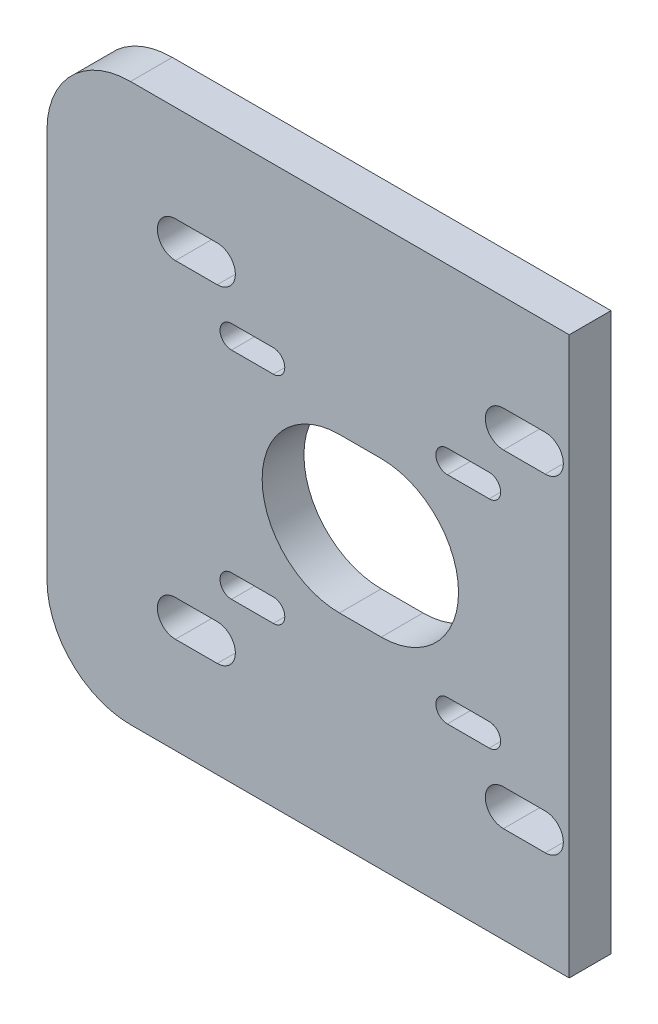
SolidWorks part; units mm, degrees
ref_plane "Alzado" through (0, 0, 0) normal (0, 0, 1) x (1, 0, 0)
ref_plane "Planta" through (0, 0, 0) normal (0, 1, 0) x (1, 0, 0)
ref_plane "Vista lateral" through (0, 0, 0) normal (1, 0, 0) x (0, 0, -1)
sketch "Croquis1" plane through (0, 0, 0) normal (0, 0, 1) x (1, 0, 0)
  line L1 (0, 0) -> (75, 0)
  line L2 (0, 0) -> (0, 80)
  line L3 (0, 80) -> (75, 80)
  line L4 (75, 0) -> (75, 80)
  dimension "D1" = 80
  dimension "D2" = 75
extrude "Saliente-Extruir1" add sketch "Croquis1" along normal blind 6
sketch "Croquis2" plane through (0, 0, 0) normal (0, 0, -1) x (-1, 0, 0)
  line L0 (0, 80) -> (0, 0) construction
  line L1 (0, 40) -> (-75, 40) construction
  line L4 (-75, 0) -> (-75, 80) construction
  line L7 (-42, 40) -> (-48, 40) construction
  line L10 (-42, 28.9) -> (-48, 28.9)
  line L19 (-42, 51.1) -> (-48, 51.1)
  line L20 (-26.5, 24.5) -> (-32.5, 24.5) construction
  line L21 (-26.5, 22.85) -> (-32.5, 22.85)
  line L22 (-26.5, 26.15) -> (-32.5, 26.15)
  line L23 (-57.5, 55.5) -> (-63.5, 55.5) construction
  line L24 (-57.5, 53.85) -> (-63.5, 53.85)
  line L25 (-57.5, 57.15) -> (-63.5, 57.15)
  line L26 (-57.5, 24.5) -> (-63.5, 24.5) construction
  line L27 (-57.5, 22.85) -> (-63.5, 22.85)
  line L28 (-57.5, 26.15) -> (-63.5, 26.15)
  line L29 (-26.5, 55.5) -> (-32.5, 55.5) construction
  line L30 (-26.5, 53.85) -> (-32.5, 53.85)
  line L31 (-26.5, 57.15) -> (-32.5, 57.15)
  line L32 (-18.45, 16.45) -> (-24.45, 16.45) construction
  line L33 (-18.45, 13.85) -> (-24.45, 13.85)
  line L34 (-18.45, 19.05) -> (-24.45, 19.05)
  line L35 (-65.55, 16.45) -> (-71.55, 16.45) construction
  line L36 (-21.45, 63.55) -> (-68.55, 63.55) construction
  line L37 (-21.45, 63.55) -> (-21.45, 16.45) construction
  line L38 (-21.45, 16.45) -> (-68.55, 16.45) construction
  line L39 (-68.55, 63.55) -> (-68.55, 16.45) construction
  line L40 (-21.45, 63.55) -> (-68.55, 16.45) construction
  line L41 (-21.45, 16.45) -> (-68.55, 63.55) construction
  line L42 (-65.55, 13.85) -> (-71.55, 13.85)
  line L43 (-65.55, 19.05) -> (-71.55, 19.05)
  line L44 (-18.45, 63.55) -> (-24.45, 63.55) construction
  line L45 (-18.45, 60.95) -> (-24.45, 60.95)
  line L46 (-18.45, 66.15) -> (-24.45, 66.15)
  line L47 (-65.55, 63.55) -> (-71.55, 63.55) construction
  line L48 (-65.55, 60.95) -> (-71.55, 60.95)
  line L49 (-65.55, 66.15) -> (-71.55, 66.15)
  arc A19 (-42, 28.9) -> (-42, 51.1) centre (-42, 40) ccw
  arc A20 (-48, 51.1) -> (-48, 28.9) centre (-48, 40) ccw
  arc A21 (-26.5, 22.85) -> (-26.5, 26.15) centre (-26.5, 24.5) ccw
  arc A22 (-32.5, 26.15) -> (-32.5, 22.85) centre (-32.5, 24.5) ccw
  arc A23 (-57.5, 53.85) -> (-57.5, 57.15) centre (-57.5, 55.5) ccw
  arc A24 (-63.5, 57.15) -> (-63.5, 53.85) centre (-63.5, 55.5) ccw
  arc A25 (-57.5, 22.85) -> (-57.5, 26.15) centre (-57.5, 24.5) ccw
  arc A26 (-63.5, 26.15) -> (-63.5, 22.85) centre (-63.5, 24.5) ccw
  arc A27 (-26.5, 53.85) -> (-26.5, 57.15) centre (-26.5, 55.5) ccw
  arc A28 (-32.5, 57.15) -> (-32.5, 53.85) centre (-32.5, 55.5) ccw
  arc A29 (-18.45, 13.85) -> (-18.45, 19.05) centre (-18.45, 16.45) ccw
  arc A30 (-24.45, 19.05) -> (-24.45, 13.85) centre (-24.45, 16.45) ccw
  arc A31 (-65.55, 13.85) -> (-65.55, 19.05) centre (-65.55, 16.45) ccw
  arc A32 (-71.55, 19.05) -> (-71.55, 13.85) centre (-71.55, 16.45) ccw
  arc A33 (-18.45, 60.95) -> (-18.45, 66.15) centre (-18.45, 63.55) ccw
  arc A34 (-24.45, 66.15) -> (-24.45, 60.95) centre (-24.45, 63.55) ccw
  arc A35 (-65.55, 60.95) -> (-65.55, 66.15) centre (-65.55, 63.55) ccw
  arc A36 (-71.55, 66.15) -> (-71.55, 60.95) centre (-71.55, 63.55) ccw
  point P6 (-45, 40)
  point P12 (-21.45, 16.45)
  point P19 (-29.5, 24.5)
  point P28 (-60.5, 55.5)
  point P35 (-60.5, 24.5)
  point P40 (-45, 40)
  point P48 (-29.5, 55.5)
  point P53 (-21.45, 16.45)
  point P56 (-68.55, 16.45)
  point P63 (-21.45, 63.55)
  point P70 (-68.55, 63.55)
  point P75 (0, 0)
  point P76 (0, 0)
  point P77 (-21.45, 63.55)
  point P78 (-68.55, 63.55)
  point P79 (-68.55, 16.45)
  dimension "D2" = 6
  dimension "D3" = 11.1
  dimension "D4" = 3.3
  dimension "D5" = 6
  dimension "D6" = 30
  dimension "D13" = 47.1
  dimension "D14" = 47.1
  dimension "D12" = 5.2
  dimension "D7" = 15.5
  dimension "D8" = 15.5
  dimension "D9" = 3.3
  dimension "D10" = 6
  dimension "D11" = 6
  dimension "D15" = 6
  dimension "D16" = 6
  dimension "D17" = 3.3
  dimension "D18" = 6
  dimension "D19" = 3.3
  dimension "D20" = 6
  dimension "D21" = 15.5
  dimension "D22" = 15.5
  dimension "D23" = 15.5
  dimension "D24" = 15.5
  dimension "D25" = 15.5
  dimension "D26" = 15.5
  dimension "D27" = 6
  dimension "D28" = 5.2
  dimension "D29" = 5.2
  dimension "D30" = 5.2
extrude "Cortar-Extruir1" cut sketch "Croquis2" against normal through all
fillet "Redondeo1" radius 12 2 edges at (0, 0, 3) (0, 80, 3)
